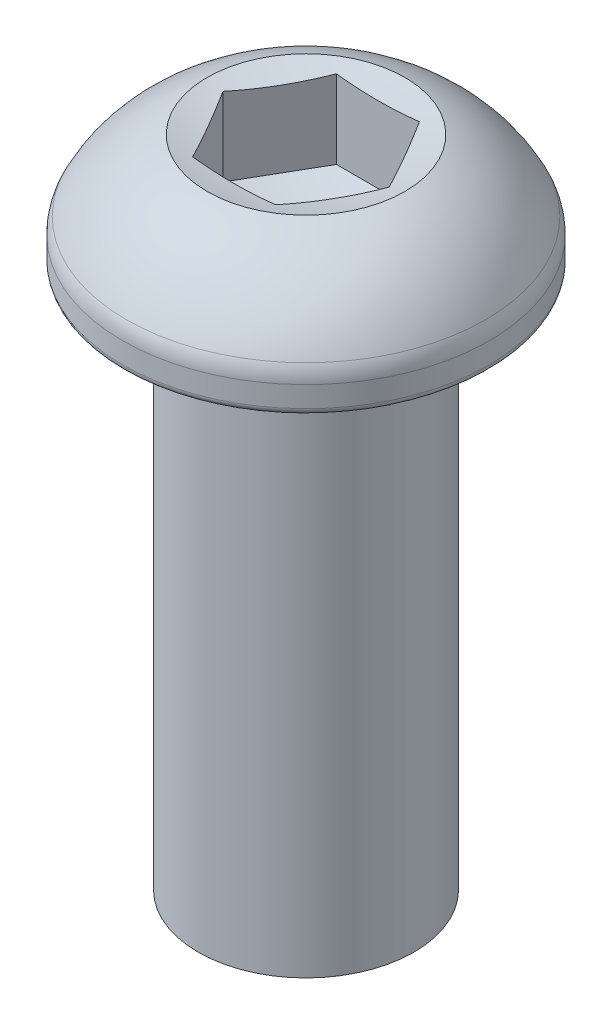
SolidWorks part; units mm, degrees
note: '?' marks a value the reader was unsure of.
material "304 STAINLESS STEEL"
ref_plane "Front Plane" through (0, 0, 0) normal (0, 0, 1) x (1, 0, 0)
ref_plane "Top Plane" through (0, 0, 0) normal (0, 1, 0) x (1, 0, 0)
ref_plane "Right Plane" through (0, 0, 0) normal (1, 0, 0) x (0, 0, -1)
ref_axis "X-Axis" through (-88.99, 0, 0) along (1, 0, 0)?
ref_axis "Y-Axis" through (0, 55, 0) along (0, -1, 0)
ref_axis "Z-Axis" through (0, 0, -88.99) along (0, 0, 1)?
sketch "Sketch1" plane through (0, 0, 0) normal (0, 0, 1) x (1, 0, 0)
  line L0 (0, 0) -> (5.1, 0)
  line L1 (5.1, 0) -> (5.1, 1)
  line L2 (0, 0) -> (0, 3.2)
  line L3 (0, 3.2) -> (2.75, 3.2)
  arc A0 (2.75, 3.2) -> (5.1, 1) centre (1.4224, -0.5733) cw
  dimension "D5" = 4
  dimension "D1" = 5.1
  dimension "D2" = 3.2
  dimension "D3" = 2.75
  dimension "D4" = 1
revolve "Revolve1" add sketch "Sketch1" angle 360 about axis through (0, 55, 0) along (0, -1, 0)
fillet "Fillet1" radius 0.2 1 edges at (0, 0, 5.1)
fillet "Fillet2" radius 1 1 edges at (0, 1, 5.1)
sketch "Sketch2" plane through (0, 0, 0) normal (0, -1, 0) x (1, 0, 0)
  circle A0 centre (0, 0) radius 3
  dimension "D1" = 6
extrude "Boss-Extrude1" add sketch "Sketch2" along normal blind 15
thread "Thread1" [suppressed] pitch 1 start angle 0, offset 2, length 0, pitch 1, diameter 6
ref_plane "Plane1" through (3, -22, 0) normal (0, 0, 1) x (1, 0, 0)
sketch "Thread Profile1" plane through (3, -22, 0) normal (0, 0, 1) x (1, 0, 0)
  line L0 (0, 0) -> (0, 1) construction
  line L11 (0, 0) -> (0, 0.875)
  line L12 (0, 0.875) -> (-0.5413, 0.5625)
  line L13 (-0.5413, 0.5625) -> (-0.5413, 0.3125)
  line L15 (-0.5413, 0.3125) -> (0, 0)
  line L17 (-0.5413, 0.4375) -> (0, 0.4375) construction
  point P2 (0, 0)
  dimension "Pitch" = 1
  dimension "Profile_Angle" = 60
  dimension "Profile_Land" = 0.25
  dimension "Profile_Height" = 0.5413
sketch "Sketch6" plane through (0, 0, 0) normal (0, 0, 1) x (1, 0, 0)
  line L0 (0, 0) -> (0, 3.2)
  line L1 (2.75, 3.2) -> (-2.75, 3.2) construction
  line L2 (0, 3.2) -> (2.75, 3.2)
  line L3 (0, 0) -> (4.9, 0)
  line L4 (4.9, 0) -> (2.75, 3.2)
  arc A0 (4.9925, 1.2306) -> (2.75, 3.2) centre (1.4224, -0.5733) ccw construction
revolve "Revolve2" add sketch "Sketch6" angle 360 about axis through (0, 55, 0) along (0, -1, 0)
sketch "Sketch7" plane through (0, 3.2, 0) normal (0, 1, 0) x (1, 0, 0)
  line L1 (1.1547, -2) -> (2.3094, 0)
  line L2 (2.3094, 0) -> (1.1547, 2)
  line L3 (1.1547, 2) -> (-1.1547, 2)
  line L4 (-1.1547, 2) -> (-2.3094, 0)
  line L5 (-2.3094, 0) -> (-1.1547, -2)
  line L6 (-1.1547, -2) -> (1.1547, -2)
  circle A0 centre (0, 0) radius 2 construction
  dimension "D1" = 4
extrude "Cut-Extrude1" cut sketch "Sketch7" against normal blind 2.3
sketch "Sketch8" plane through (0, 0, 0) normal (0, 0, 1) x (1, 0, 0)
  line L0 (0, 0.9) -> (0, 0.5)
  line L1 (0, 0.9) -> (2.3094, 0.9)
  line L2 (1.1547, 0.9) -> (-1.1547, 0.9) construction
  line L3 (1.1547, 0.9) -> (-1.1547, 0.9) construction
  line L4 (-2.3094, 0.9) -> (-2.3094, 3.2) construction
  line L5 (-2.3094, 0.9) -> (-2.3094, 3.2) construction
  line L6 (2.3094, 0.9) -> (2.3094, 3.2) construction
  line L7 (2.3094, 0.9) -> (2.3094, 3.2) construction
  line L8 (0, 0.5) -> (0.25, 0.5)
  arc A1 (0.25, 0.5) -> (2.3094, 0.9) centre (0.25, 6.0014) ccw
  dimension "D2" = 0.25
  dimension "D1" = 0.4
revolve "Cut-Revolve1" cut sketch "Sketch8" angle 360 about axis through (0, 55, 0) along (0, -1, 0)
sketch "Sketch9" plane through (0, 0, 0) normal (0, 0, 1) x (1, 0, 0)
  line L0 (2.75, 3.2) -> (-2.75, 3.2) construction
  line L1 (2.75, 3.2) -> (-2.75, 3.2)
  line L2 (0, 3.2) -> (0, 2.8144)
  line L3 (0, 2.8144) -> (-2.75, 2.8144) construction
  arc A0 (2.75, 3.2) -> (0, 2.8144) centre (0, 12.8144) cw
  dimension "D1" = 10
revolve "Cut-Revolve2" cut sketch "Sketch9" angle 360 about axis through (0, 55, 0) along (0, -1, 0)
sketch "Sketch10" [suppressed] plane through (0, 0, 0) normal (0, 0, 1) x (1, 0, 0)
  line L0 (3, -19.6) -> (3, -20)
  line L1 (3, -20) -> (2.4, -20)
  line L2 (2.4, -20) -> (3, -19.6)
  line L3 (-2.2716, -20) -> (2.1213, -20) construction
  line L4 (3, -19.125) -> (3, -19) construction
  dimension "D1" = 0.4
  dimension "D2" = 0.6
revolve "Cut-Revolve3" [suppressed] cut sketch "Sketch10" angle 360 about axis through (0, 55, 0) along (0, -1, 0)
equation "\"length\"= 15"
equation "\"D1@Boss-Extrude1\"=\"length\""
